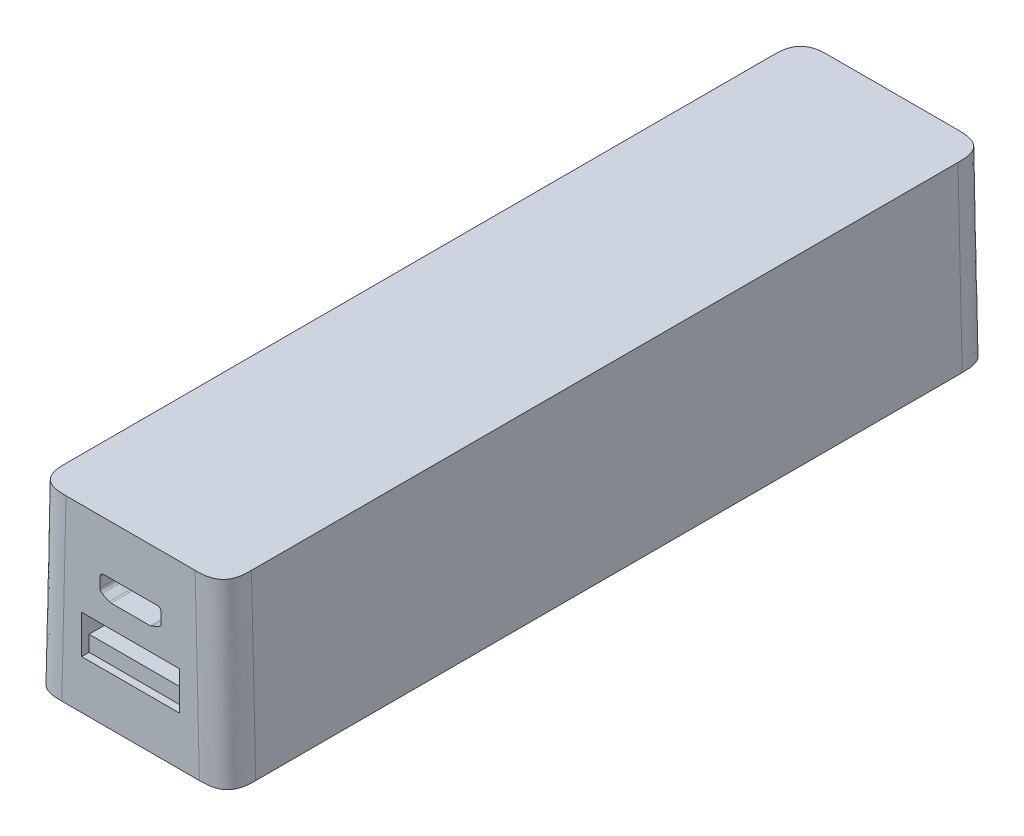
SolidWorks part; units mm, degrees
ref_plane "Front Plane" through (0, 0, 0) normal (0, 0, 1) x (1, 0, 0)
ref_plane "Top Plane" through (0, 0, 0) normal (0, 1, 0) x (1, 0, 0)
ref_plane "Right Plane" through (0, 0, 0) normal (1, 0, 0) x (0, 0, -1)
sketch "Sketch1" plane through (0, 0, 0) normal (0, 0, 1) x (1, 0, 0)
  line L0 (0, 0) -> (0, 11.5) construction
  line L5 (12.395, -11.5) -> (-12.395, -11.5)
  line L9 (-12.395, -11.5) -> (-11.85, 11.5)
  line L10 (12.395, -11.5) -> (11.85, 11.5)
  line L11 (-11.85, 11.5) -> (11.85, 11.5)
  point P0 (0, 0)
  dimension "D3" = 23.7
  dimension "D1" = 23
  dimension "D2" = 24.79
extrude "Boss-Extrude2" add sketch "Sketch1" along normal blind 97.5
fillet "Fillet4" radius 3.6 4 edges at (-12.1225, 0, 0) (12.1225, 0, 0) (-12.1225, 0, 97.5) (12.1225, 0, 97.5) curvature continuous yes
sketch "Sketch2" plane through (0, 0, 97.5) normal (0, 0, 1) x (1, 0, 0)
  line L0 (0, -11.5) -> (0, 11.5) construction
  line L1 (-8.794, -11.5) -> (8.794, -11.5) construction
  line L2 (8.249, 11.5) -> (-8.249, 11.5) construction
  line L4 (6.25, -5.3) -> (-6.25, -5.3)
  line L5 (6.25, -5.3) -> (6.25, -0.39)
  line L6 (6.25, -0.39) -> (-6.25, -0.39)
  line L7 (-6.25, -5.3) -> (-6.25, -0.39)
  line L8 (6.25, -5.3) -> (-6.25, -0.39) construction
  line L9 (6.25, -0.39) -> (-6.25, -5.3) construction
  point P6 (0, -2.845)
  dimension "D1" = 6.2
  dimension "D2" = 11.11
  dimension "D3" = 12.5
extrude "Cut-Extrude1" cut sketch "Sketch2" against normal blind 9.85
sketch "Sketch3" plane through (0, 0, 97.5) normal (0, 0, 1) x (1, 0, 0)
  line L0 (-3.6292, 2.9946) -> (-2.7192, 2.5506)
  line L1 (2.5, 2.5) -> (-2.5, 2.5)
  line L2 (3.91, 3.444) -> (3.91, 4.7)
  line L3 (3.41, 5.2) -> (-3.41, 5.2)
  line L4 (-3.91, 3.444) -> (-3.91, 4.7)
  line L5 (3.9802, 3.1658) -> (-3.91, 5.2) construction
  line L6 (3.91, 5.2) -> (-3.9802, 3.1658) construction
  line L7 (0, 5.2) -> (0, 2.5) construction
  line L8 (3.6292, 2.9946) -> (2.7192, 2.5506)
  line L9 (-8.794, -11.5) -> (8.794, -11.5) construction
  arc A0 (-2.7192, 2.5506) -> (-2.5, 2.5) centre (-2.5, 3) ccw
  arc A1 (2.5, 2.5) -> (2.7192, 2.5506) centre (2.5, 3) ccw
  arc A2 (3.91, 3.444) -> (3.6292, 2.9946) centre (3.41, 3.444) cw
  arc A3 (-3.6292, 2.9946) -> (-3.91, 3.444) centre (-3.41, 3.444) cw
  arc A4 (3.91, 4.7) -> (3.41, 5.2) centre (3.41, 4.7) ccw
  arc A5 (-3.91, 4.7) -> (-3.41, 5.2) centre (-3.41, 4.7) cw
  point P0 (0, 4.192)
  point P14 (-2.6155, 2.5)
  point P17 (2.6155, 2.5)
  point P20 (3.91, 3.1316)
  point P23 (-3.91, 3.1316)
  dimension "D3" = 0.5
  dimension "D1" = 2.7
  dimension "D2" = 7.82
  dimension "D4" = 5
  dimension "D5" = 14
extrude "Cut-Extrude2" cut sketch "Sketch3" against normal blind 10
sketch "Sketch4" plane through (0, 0, 87.65) normal (0, 0, 1) x (1, 0, 0)
  line L1 (-6.1595, -3.1989) -> (6.196, -3.1989)
  line L2 (-6.1595, -3.1989) -> (-6.1595, -5.1989)
  line L3 (-6.1595, -5.1989) -> (6.196, -5.1989)
  line L4 (6.196, -3.1989) -> (6.196, -5.1989)
  dimension "D1" = 2
extrude "Boss-Extrude3" add sketch "Sketch4" along normal blind 9
